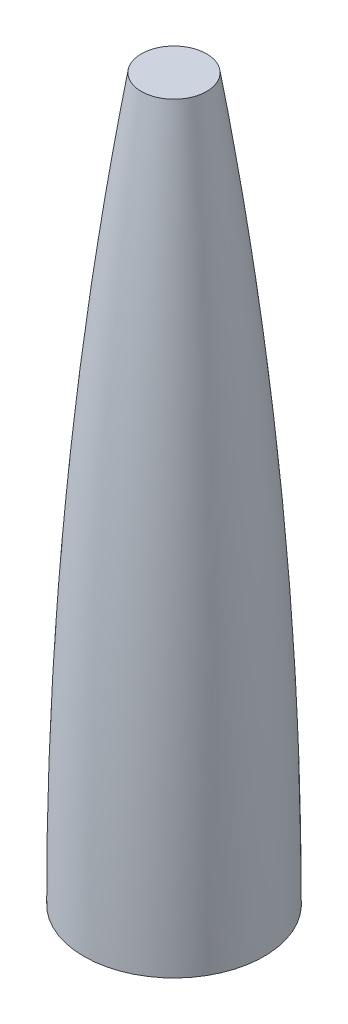
SolidWorks part; units mm, degrees
material "E-Glass Fiber"
ref_plane "Front Plane" through (0, 0, 0) normal (0, 0, 1) x (1, 0, 0)
ref_plane "Top Plane" through (0, 0, 0) normal (0, 1, 0) x (1, 0, 0)
ref_plane "Right Plane" through (0, 0, 0) normal (1, 0, 0) x (0, 0, -1)
sketch "Sketch1" plane through (0, 0, 0) normal (0, 0, 1) x (1, 0, 0)
  line L1 (0, 0) -> (0, 812.8)
  line L2 (-101.6, 0) -> (0, 0) construction
  line L3 (0, 812.8) -> (-36.8107, 812.8)
  line L4 (0, 1016) -> (0, 812.8) construction
  line L5 (-98.425, 0) -> (-98.425, -101.6)
  line L6 (-98.425, -101.6) -> (0, -101.6)
  line L7 (0, 0) -> (0, -101.6)
  line L8 (-98.425, 0) -> (-101.6, 0)
  arc A0 (0, 1016) -> (-36.8107, 812.8) centre (5029.2, 0) ccw construction
  spline S0 degree 4 poles (-23.2398, 893.2866) (-23.5393, 891.5924) (-24.137, 888.2033) (-25.0296, 883.1148) (-26.2088, 876.3394) (-27.3767, 869.5744) (-28.525, 862.8715) (-29.6693, 856.1347) (-30.7805, 849.5464) (-31.9198, 842.7267) (-32.9792, 836.3481) (-34.1672, 829.1125) (-35.0792, 823.5406) (-36.435, 815.1441) (-37.0457, 811.3406) (-38.406, 802.8129) (-39.4063, 796.4669) (-40.5094, 789.4175) (-41.5637, 782.6088) (-42.4113, 777.0973) (-43.2542, 771.5761) (-44.0966, 766.0177) (-44.9373, 760.4296) (-45.7763, 754.8098) (-46.8172, 747.7841) (-48.054, 739.3514) (-49.4786, 729.5106) (-51.8836, 712.6352) (-56.1784, 681.6809) (-64.3109, 619.7097) (-79.957, 484.2341) (-91.5619, 342.6137) (-98.2797, 206.3794) (-100.6652, 101.2886) (-101.1219, 71.4617) (-101.3057, 55.1272) (-101.3623, 49.4455) (-101.4013, 45.2149) (-101.437, 41.0149) (-101.474, 36.1352) (-101.5101, 30.575) (-101.5403, 25.0243) (-101.5644, 19.4326) (-101.5824, 13.9273) (-101.5945, 8.4855) (-101.6008, 1.478) (-101.6004, -2.3538) (-101.5919, -10.831) (-101.5742, -16.4582) (-101.5477, -23.7538) (-101.5124, -30.1968) (-101.4682, -37.0784) (-101.4152, -43.7331) (-101.3531, -50.5363) (-101.2817, -57.3091) (-101.201, -64.1452) (-101.1107, -70.9945) (-101.0361, -76.1392) (-100.9833, -79.5663) (-100.9562, -81.2797) knots 0 0 0 0 0 0.007031 0.014061 0.021092 0.028122 0.035027 0.041932 0.048837 0.055742 0.062647 0.069552 0.076457 0.083362 0.08904 0.094718 0.106073 0.111751 0.117429 0.123106 0.128784 0.134587 0.14039 0.146193 0.151996 0.163602 0.175208 0.186814 0.221632 0.291267 0.430538 0.743898 0.801928 0.848352 0.859958 0.865761 0.868662 0.871564 0.877241 0.882919 0.888597 0.894275 0.899952 0.90563 0.911308 0.916985 0.923861 0.930737 0.937613 0.944488 0.951364 0.95824 0.965115 0.971991 0.978993 0.985996 0.992998 1 1 1 1 1 construction
  spline S1 degree 4 poles (-36.8107, 812.8) (-36.9943, 811.656) (-37.3629, 809.3523) (-38.406, 802.8129) (-39.4063, 796.4669) (-40.5094, 789.4175) (-41.5637, 782.6088) (-42.4113, 777.0973) (-43.2542, 771.5761) (-44.0966, 766.0177) (-44.9373, 760.4296) (-45.7763, 754.8098) (-46.8172, 747.7841) (-48.054, 739.3514) (-49.4786, 729.5106) (-51.8836, 712.6352) (-56.1784, 681.6809) (-64.3109, 619.7097) (-79.957, 484.2341) (-91.5619, 342.6137) (-98.2797, 206.3794) (-100.6652, 101.2886) (-101.1219, 71.4617) (-101.3057, 55.1272) (-101.3623, 49.4455) (-101.4013, 45.2149) (-101.437, 41.0149) (-101.474, 36.1352) (-101.5101, 30.575) (-101.5403, 25.0243) (-101.5644, 19.4326) (-101.5824, 13.9273) (-101.5945, 8.4855) (-101.599, 3.4932) (-101.6, 1.1586) (-101.6, 0) knots 0.083362 0.083362 0.083362 0.083362 0.083362 0.08904 0.094718 0.106073 0.111751 0.117429 0.123106 0.128784 0.134587 0.14039 0.146193 0.151996 0.163602 0.175208 0.186814 0.221632 0.291267 0.430538 0.743898 0.801928 0.848352 0.859958 0.865761 0.868662 0.871564 0.877241 0.882919 0.888597 0.894275 0.899952 0.90563 0.911308 0.916985 0.916985 0.916985 0.916985 0.916985
  dimension "D2" = 1016
  dimension "D1" = 203.2
  dimension "D3" = 101.6
  dimension "D4" = 3.175
revolve "Revolve1" add sketch "Sketch1" angle 360 about L1 region at (-43.2688, 298.0469, 0)
shell "Shell1" thickness 3.175 removed face at (0, -101.6, -98.425)
sketch3d "3DSketch1" plane through (0, 0, 0) normal (0, 0, 1) x (1, 0, 0)
  dimension "D1" = 101.6
sketch "Sketch2" plane through (0, 0, 101.6) normal (0, 0, 1) x (1, 0, 0)
  line L1 (-98.425, -101.6) -> (98.425, -101.6)
  line L2 (-98.425, -101.6) -> (-98.425, 0)
  line L3 (-98.425, 0) -> (98.425, 0)
  line L4 (98.425, -101.6) -> (98.425, 0)
extrude "Cut-Extrude1" cut sketch "Sketch2" against normal through all contours L3 L4 L1 L2
sketch "Sketch3" plane through (0, 0, 0) normal (0, 0, 1) x (1, 0, 0)
  line L0 (0, 0) -> (0, 152.4) construction
  circle A0 centre (0, 152.4) radius 3.175
  dimension "D2" = 6.35
  dimension "D1" = 152.4
equation "\"R\"= 4in"
equation "\"L\"= 40in"
equation "\"D2@Sketch1\" = \"L\""
equation "\"p\"= ( \"R\" ^ 2 + \"L\" ^ 2 ) / ( \"R\" * 2 )"
equation "\"tip_Length\"= ( \"R\" * 2 )"
equation "\"D1@Sketch1\"=\"tip_Length\""
